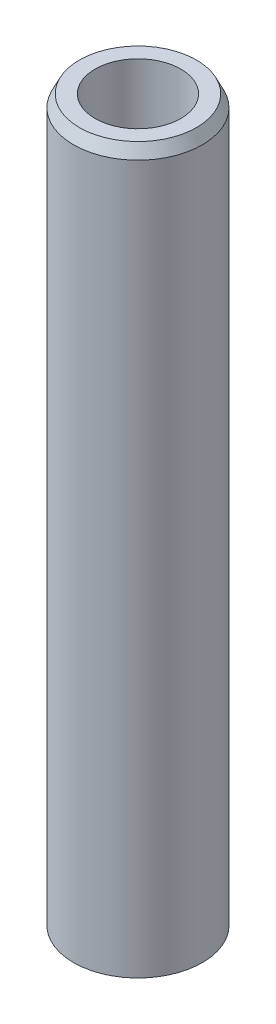
SolidWorks part; units mm, degrees
ref_plane "Front Plane" through (0, 0, 0) normal (0, 0, 1) x (1, 0, 0)
ref_plane "Top Plane" through (0, 0, 0) normal (0, 1, 0) x (1, 0, 0)
ref_plane "Right Plane" through (0, 0, 0) normal (1, 0, 0) x (0, 0, -1)
sketch "Sketch1" plane through (0, 0, 0) normal (0, 1, 0) x (1, 0, 0)
  circle A0 centre (0, 0) radius 27.5
  dimension "SHAFT_OD" = 55
extrude "Boss-Extrude1" add sketch "Sketch1" along normal blind 310.016
sketch "Sketch2" plane through (0, 0, 0) normal (0, 1, 0) x (1, 0, 0)
  circle A0 centre (0, 0) radius 18.3058
  dimension "BORE_D" = 36.6116
extrude "Cut-Extrude1" cut sketch "Sketch2" along normal through all
chamfer "Chamfer1" distance 5.1223 angle 26.071 2 edges at (0, 310.016, 27.5) (0, 0, 27.5) first distance on face at (0, 310.016, 27.5) first distance on face at (0, 0, 18.3058)
